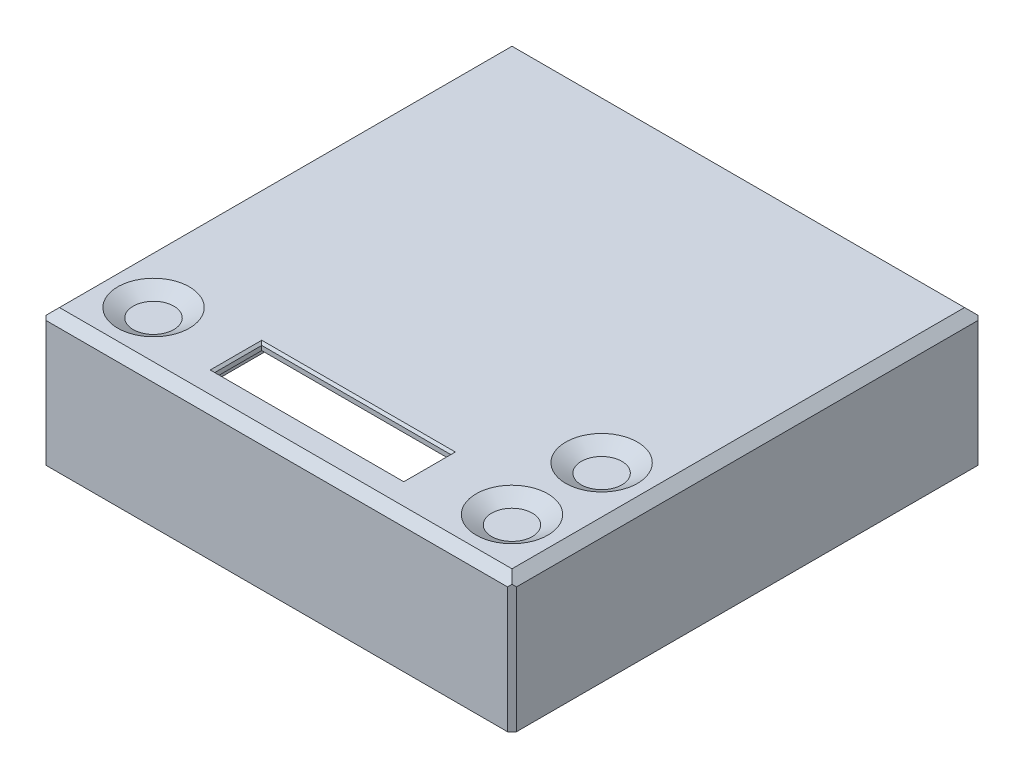
SolidWorks part; units mm, degrees
ref_plane "前视基准面" through (0, 0, 0) normal (0, 0, 1) x (1, 0, 0)
ref_plane "上视基准面" through (0, 0, 0) normal (0, 1, 0) x (1, 0, 0)
ref_plane "右视基准面" through (0, 0, 0) normal (1, 0, 0) x (0, 0, -1)
other "Configuration Table"
sketch "草图1" plane through (0, 0, 0) normal (0, 1, 0) x (1, 0, 0)
  line L0 (-45, 45) -> (45, 45) construction
  line L1 (-50, 50) -> (50, 50)
  line L2 (-50, 50) -> (-50, -50)
  line L3 (-50, -50) -> (50, -50)
  line L4 (50, 50) -> (50, -50)
  line L5 (-50, 50) -> (50, -50) construction
  line L6 (-50, -50) -> (50, 50) construction
  line L7 (-30, -30) -> (30, -30) construction
  line L8 (-40, -40) -> (40, -40) construction
  line L9 (40, -40) -> (40, -20) construction
  line L11 (28, -31) -> (-24, -31)
  line L12 (28, -31) -> (28, -49)
  line L13 (28, -49) -> (-24, -49)
  line L14 (-24, -31) -> (-24, -49)
  circle A0 centre (-45, 45) radius 1.75
  circle A1 centre (45, 45) radius 1.75
  circle A2 centre (-30, -30) radius 1.75
  circle A3 centre (30, -30) radius 1.75
  circle A4 centre (-40, -40) radius 5
  circle A5 centre (40, -40) radius 5
  circle A6 centre (40, -20) radius 5
  point P0 (0, 0)
  dimension "D4" = 3.5
  dimension "D8" = 10
  dimension "D1" = 100
  dimension "D2" = 100
  dimension "D3" = 5
  dimension "D5" = 20
  dimension "D6" = 10
  dimension "D7" = 20
  dimension "D9" = 52
  dimension "D10" = 18
  dimension "D11" = 1
  dimension "D12" = 22
sketch "草图2" plane through (0, 0, 0) normal (0, 1, 0) x (1, 0, 0)
  line L0 (50, 50) -> (50, -50) construction
  line L1 (-50.5, 50.5) -> (50.5, 50.5)
  line L2 (-50.5, 50.5) -> (-50.5, -50.5)
  line L3 (-50.5, -50.5) -> (50.5, -50.5)
  line L4 (50.5, 50.5) -> (50.5, -50.5)
  line L5 (-50.5, 50.5) -> (50.5, -50.5) construction
  line L6 (-50.5, -50.5) -> (50.5, 50.5) construction
  line L7 (-50, -50) -> (50, -50) construction
  line L9 (-52.5, 52.5) -> (52.5, 52.5)
  line L10 (-52.5, 52.5) -> (-52.5, -52.5)
  line L11 (-52.5, -52.5) -> (52.5, -52.5)
  line L12 (52.5, 52.5) -> (52.5, -52.5)
  line L13 (-52.5, 52.5) -> (52.5, -52.5) construction
  line L14 (-52.5, -52.5) -> (52.5, 52.5) construction
  point P0 (0, 0)
  point P10 (0, 0)
  dimension "D1" = 0.5
  dimension "D2" = 0.5
  dimension "D3" = 2
  dimension "D4" = 2
extrude "凸台-拉伸1" add sketch "草图2" against normal blind 25
extrude "凸台-拉伸2" add sketch "草图2<2>" along normal blind 5 contours L11 L12 L9 L10
sketch "草图2<2>" plane through (0, 0, 0) normal (0, 1, 0) x (1, 0, 0) same geometry as "草图2"
sketch "草图3" plane through (0, 0, 0) normal (0, 1, 0) x (1, 0, 0)
  line L0 (28, -31) -> (28, -49) construction
  line L1 (28, -49) -> (-24, -49) construction
  line L2 (-24, -31) -> (-24, -49) construction
  line L3 (28, -31) -> (-24, -31) construction
  line L4 (28, -31) -> (28, -35)
  line L5 (28, -49) -> (-24, -49)
  line L6 (-24, -31) -> (-24, -49)
  line L7 (28, -31) -> (-24, -31)
  line L8 (28, -35) -> (28, -45) construction
  line L9 (28, -35) -> (30, -35)
  line L10 (28, -35) -> (28, -45) construction
  line L11 (28, -45) -> (30, -45)
  line L12 (30, -35) -> (30, -45)
  line L13 (28, -45) -> (28, -49)
  circle A0 centre (-30, -30) radius 2
  circle A1 centre (-45, 45) radius 2
  circle A2 centre (45, 45) radius 2
  point P17 (-24, -40)
  point P18 (30, -40)
  dimension "D1" = 4
  dimension "D2" = 10
  dimension "D3" = 2
extrude "切除-拉伸1" cut sketch "草图3" along normal blind 3.5
sketch "草图4" plane through (0, 0, 0) normal (0, 1, 0) x (1, 0, 0)
  circle A0 centre (30, -30) radius 1.5
  dimension "D1" = 3
extrude "凸台-拉伸3" add sketch "草图4" against normal blind 3
sketch "草图6" plane through (0, 0, 0) normal (0, 0, 1) x (1, 0, 0)
  line L1 (4.5, -1.5) -> (-4.5, -1.5)
  line L2 (4.5, -1.5) -> (4.5, -4.7)
  line L3 (4.5, -4.7) -> (-4.5, -4.7)
  line L4 (-4.5, -1.5) -> (-4.5, -4.7)
  line L5 (4.5, -1.5) -> (-4.5, -4.7) construction
  line L6 (4.5, -4.7) -> (-4.5, -1.5) construction
  point P0 (0, -3.1)
  dimension "D1" = 1.5
  dimension "D2" = 9
  dimension "D3" = 3.2
extrude "切除-拉伸3" cut sketch "草图6" against normal through all
chamfer "倒角3" distance 2 angle 45 4 edges at (0, 5, 52.5) (52.5, 5, 0) (0, 5, -52.5) (-52.5, 5, 0)
chamfer "倒角2" distance 1 angle 45 4 edges at (-52.5, -11, -52.5) (52.5, -11, -52.5) (52.5, -11, 52.5) (-52.5, -11, 52.5)
sketch "草图7" plane through (0, 0, 0) normal (0, 1, 0) x (1, 0, 0)
  circle A0 centre (-40, -40) radius 8
  circle A1 centre (40, -40) radius 8
  circle A2 centre (40, -20) radius 8
  dimension "D1" = 16
extrude "切除-拉伸4" cut sketch "草图7" against normal blind 2 from surface starting at face at (0, 5, 0)
chamfer "倒角4" distance 2 angle 60 3 edges at (40, 3, 48) (40, 3, 28) (-40, 3, 48) first distance on face at (40, 3, 48) first distance on face at (40, 3, 28) first distance on face at (-40, 3, 48)
sketch "草图8" plane through (0, 0, 0) normal (0, 1, 0) x (1, 0, 0)
  line L0 (-40, -40) -> (40, -40) construction
  line L1 (-21.6, -34.25) -> (21.6, -34.25)
  line L2 (-21.6, -34.25) -> (-21.6, -45.75)
  line L3 (-21.6, -45.75) -> (21.6, -45.75)
  line L4 (21.6, -34.25) -> (21.6, -45.75)
  line L5 (-21.6, -34.25) -> (21.6, -45.75) construction
  line L6 (-21.6, -45.75) -> (21.6, -34.25) construction
  point P0 (0, -40)
  dimension "D1" = 43.2
  dimension "D2" = 11.5
extrude "切除-拉伸5" cut sketch "草图8" against normal blind 0.5 from surface starting at face at (-40, 5, 48)
chamfer "倒角5" distance 0.5 angle 45 4 edges at (0, 4.5, 45.75) (21.6, 4.5, 40) (-21.6, 4.5, 40) (0, 4.5, 34.25)
sketch "草图9" plane through (0, 0, 0) normal (0, 1, 0) x (1, 0, 0)
  line L0 (16.1333, -33.3167) -> (16.1333, -26.8167) construction
  line L1 (50.5, 35.4167) -> (35.4167, 35.4167)
  line L2 (50.5, 35.4167) -> (50.5, 39.5)
  line L3 (39.5, 50.5) -> (35.4167, 50.5)
  line L4 (35.4167, 35.4167) -> (35.4167, 50.5)
  line L5 (33.3167, 35.4167) -> (33.3167, 50.5)
  line L6 (33.3167, 35.4167) -> (18.2333, 35.4167)
  line L7 (18.2333, 35.4167) -> (18.2333, 50.5)
  line L8 (33.3167, 50.5) -> (18.2333, 50.5)
  line L9 (16.1333, 35.4167) -> (16.1333, 50.5)
  line L10 (16.1333, 35.4167) -> (1.05, 35.4167)
  line L11 (1.05, 35.4167) -> (1.05, 50.5)
  line L12 (16.1333, 50.5) -> (1.05, 50.5)
  line L13 (-1.05, 35.4167) -> (-1.05, 50.5)
  line L14 (-1.05, 35.4167) -> (-16.1333, 35.4167)
  line L15 (-16.1333, 35.4167) -> (-16.1333, 50.5)
  line L16 (-1.05, 50.5) -> (-16.1333, 50.5)
  line L17 (-18.2333, 35.4167) -> (-18.2333, 50.5)
  line L18 (-18.2333, 35.4167) -> (-33.3167, 35.4167)
  line L19 (-33.3167, 35.4167) -> (-33.3167, 50.5)
  line L20 (-18.2333, 50.5) -> (-33.3167, 50.5)
  line L21 (-35.4167, 35.4167) -> (-35.4167, 50.5)
  line L22 (-35.4167, 35.4167) -> (-50.5, 35.4167)
  line L23 (-50.5, 35.4167) -> (-50.5, 39.5)
  line L24 (-35.4167, 50.5) -> (-39.5, 50.5)
  line L25 (33.3167, 18.2333) -> (33.3167, 33.3167)
  line L26 (33.3167, 18.2333) -> (18.2333, 18.2333)
  line L27 (18.2333, 18.2333) -> (18.2333, 33.3167)
  line L28 (33.3167, 33.3167) -> (18.2333, 33.3167)
  line L29 (16.1333, 18.2333) -> (16.1333, 33.3167)
  line L30 (16.1333, 18.2333) -> (1.05, 18.2333)
  line L31 (1.05, 18.2333) -> (1.05, 33.3167)
  line L32 (16.1333, 33.3167) -> (1.05, 33.3167)
  line L33 (-1.05, 18.2333) -> (-1.05, 33.3167)
  line L34 (-1.05, 18.2333) -> (-16.1333, 18.2333)
  line L35 (-16.1333, 18.2333) -> (-16.1333, 33.3167)
  line L36 (-1.05, 33.3167) -> (-16.1333, 33.3167)
  line L37 (-18.2333, 18.2333) -> (-18.2333, 33.3167)
  line L38 (-18.2333, 18.2333) -> (-33.3167, 18.2333)
  line L39 (-33.3167, 18.2333) -> (-33.3167, 33.3167)
  line L40 (-18.2333, 33.3167) -> (-33.3167, 33.3167)
  line L41 (-35.4167, 18.2333) -> (-35.4167, 33.3167)
  line L42 (-35.4167, 18.2333) -> (-50.5, 18.2333)
  line L43 (-50.5, 18.2333) -> (-50.5, 33.3167)
  line L44 (-35.4167, 33.3167) -> (-50.5, 33.3167)
  line L45 (33.3167, 1.05) -> (33.3167, 16.1333)
  line L46 (33.3167, 1.05) -> (18.2333, 1.05)
  line L47 (18.2333, 1.05) -> (18.2333, 16.1333)
  line L48 (33.3167, 16.1333) -> (18.2333, 16.1333)
  line L49 (16.1333, 1.05) -> (16.1333, 16.1333)
  line L50 (16.1333, 1.05) -> (1.05, 1.05)
  line L51 (1.05, 1.05) -> (1.05, 16.1333)
  line L52 (16.1333, 16.1333) -> (1.05, 16.1333)
  line L53 (-1.05, 1.05) -> (-1.05, 16.1333)
  line L54 (-1.05, 1.05) -> (-16.1333, 1.05)
  line L55 (-16.1333, 1.05) -> (-16.1333, 16.1333)
  line L56 (-1.05, 16.1333) -> (-16.1333, 16.1333)
  line L57 (-18.2333, 1.05) -> (-18.2333, 16.1333)
  line L58 (-18.2333, 1.05) -> (-33.3167, 1.05)
  line L59 (-33.3167, 1.05) -> (-33.3167, 16.1333)
  line L60 (-18.2333, 16.1333) -> (-33.3167, 16.1333)
  line L61 (-35.4167, 1.05) -> (-35.4167, 16.1333)
  line L62 (-35.4167, 1.05) -> (-50.5, 1.05)
  line L63 (-50.5, 1.05) -> (-50.5, 16.1333)
  line L64 (-35.4167, 16.1333) -> (-50.5, 16.1333)
  line L65 (33.3167, -16.1333) -> (33.3167, -1.05)
  line L66 (33.3167, -16.1333) -> (18.2333, -16.1333)
  line L67 (18.2333, -16.1333) -> (18.2333, -1.05)
  line L68 (33.3167, -1.05) -> (18.2333, -1.05)
  line L69 (16.1333, -16.1333) -> (16.1333, -1.05)
  line L70 (16.1333, -16.1333) -> (1.05, -16.1333)
  line L71 (1.05, -16.1333) -> (1.05, -1.05)
  line L72 (16.1333, -1.05) -> (1.05, -1.05)
  line L73 (-1.05, -16.1333) -> (-1.05, -1.05)
  line L74 (-1.05, -16.1333) -> (-16.1333, -16.1333)
  line L75 (-16.1333, -16.1333) -> (-16.1333, -1.05)
  line L76 (-1.05, -1.05) -> (-16.1333, -1.05)
  line L77 (-18.2333, -16.1333) -> (-18.2333, -1.05)
  line L78 (-18.2333, -16.1333) -> (-33.3167, -16.1333)
  line L79 (-33.3167, -16.1333) -> (-33.3167, -1.05)
  line L80 (-18.2333, -1.05) -> (-33.3167, -1.05)
  line L81 (-35.4167, -16.1333) -> (-35.4167, -1.05)
  line L82 (-35.4167, -16.1333) -> (-50.5, -16.1333)
  line L83 (-50.5, -16.1333) -> (-50.5, -1.05)
  line L84 (-35.4167, -1.05) -> (-50.5, -1.05)
  line L85 (33.3167, -33.3167) -> (33.3167, -18.2333) construction
  line L86 (33.3167, -33.3167) -> (18.2333, -33.3167) construction
  line L87 (18.2333, -26.8167) -> (18.2333, -18.2333)
  line L88 (32, -18.2333) -> (18.2333, -18.2333)
  line L89 (16.1333, -26.8167) -> (16.1333, -18.2333)
  line L90 (16.1333, -33.3167) -> (1.05, -33.3167) construction
  line L91 (1.05, -26.8167) -> (1.05, -18.2333)
  line L92 (16.1333, -18.2333) -> (1.05, -18.2333)
  line L93 (-1.05, -26.8167) -> (-1.05, -18.2333)
  line L94 (-1.05, -33.3167) -> (-16.1333, -33.3167) construction
  line L95 (-16.1333, -26.8167) -> (-16.1333, -18.2333)
  line L96 (-1.05, -18.2333) -> (-16.1333, -18.2333)
  line L97 (-18.2333, -26.8167) -> (-18.2333, -18.2333)
  line L98 (-18.2333, -33.3167) -> (-33.3167, -33.3167) construction
  line L99 (-33.3167, -26.8167) -> (-33.3167, -18.2333)
  line L100 (-18.2333, -18.2333) -> (-33.3167, -18.2333)
  line L101 (-35.4167, -32) -> (-35.4167, -18.2333)
  line L102 (-35.4167, -33.3167) -> (-50.5, -33.3167) construction
  line L103 (-50.5, -32) -> (-50.5, -18.2333)
  line L104 (-35.4167, -18.2333) -> (-50.5, -18.2333)
  line L105 (33.3167, -50.5) -> (33.3167, -35.4167) construction
  line L106 (33.3167, -50.5) -> (18.2333, -50.5) construction
  line L107 (18.2333, -50.5) -> (18.2333, -35.4167) construction
  line L108 (33.3167, -35.4167) -> (18.2333, -35.4167) construction
  line L109 (16.1333, -50.5) -> (16.1333, -35.4167) construction
  line L110 (16.1333, -50.5) -> (1.05, -50.5) construction
  line L111 (1.05, -50.5) -> (1.05, -35.4167) construction
  line L112 (16.1333, -35.4167) -> (1.05, -35.4167) construction
  line L113 (-1.05, -50.5) -> (-1.05, -35.4167) construction
  line L114 (-1.05, -50.5) -> (-16.1333, -50.5) construction
  line L115 (-16.1333, -50.5) -> (-16.1333, -35.4167) construction
  line L116 (-1.05, -35.4167) -> (-16.1333, -35.4167) construction
  line L117 (-18.2333, -50.5) -> (-18.2333, -35.4167) construction
  line L118 (-18.2333, -50.5) -> (-33.3167, -50.5) construction
  line L119 (-33.3167, -50.5) -> (-33.3167, -35.4167) construction
  line L120 (-18.2333, -35.4167) -> (-33.3167, -35.4167) construction
  line L121 (-35.4167, -50.5) -> (-35.4167, -35.4167) construction
  line L122 (-35.4167, -50.5) -> (-50.5, -50.5) construction
  line L123 (-50.5, -50.5) -> (-50.5, -35.4167) construction
  line L124 (-35.4167, -35.4167) -> (-50.5, -35.4167) construction
  line L125 (50.5, 18.2333) -> (50.5, 33.3167)
  line L126 (50.5, 18.2333) -> (35.4167, 18.2333)
  line L127 (35.4167, 18.2333) -> (35.4167, 33.3167)
  line L128 (50.5, 33.3167) -> (35.4167, 33.3167)
  line L129 (50.5, 1.05) -> (50.5, 16.1333)
  line L130 (50.5, 1.05) -> (35.4167, 1.05)
  line L131 (35.4167, 1.05) -> (35.4167, 16.1333)
  line L132 (50.5, 16.1333) -> (35.4167, 16.1333)
  line L133 (50.5, -12) -> (50.5, -1.05)
  line L134 (50.5, -16.1333) -> (35.4167, -16.1333) construction
  line L135 (35.4167, -12) -> (35.4167, -1.05)
  line L136 (50.5, -1.05) -> (35.4167, -1.05)
  line L137 (50.5, -33.3167) -> (50.5, -18.2333) construction
  line L138 (50.5, -33.3167) -> (35.4167, -33.3167) construction
  line L139 (35.4167, -33.3167) -> (35.4167, -18.2333) construction
  line L140 (50.5, -18.2333) -> (35.4167, -18.2333) construction
  line L141 (50.5, -50.5) -> (50.5, -35.4167) construction
  line L142 (50.5, -50.5) -> (35.4167, -50.5) construction
  line L143 (35.4167, -50.5) -> (35.4167, -35.4167) construction
  line L144 (50.5, -35.4167) -> (35.4167, -35.4167) construction
  line L145 (-50.5, 50.5) -> (-50.5, -50.5) construction
  line L146 (-50.5, -50.5) -> (50.5, -50.5) construction
  line L147 (50.5, -50.5) -> (50.5, 50.5) construction
  line L148 (32, -26.8167) -> (18.2333, -26.8167)
  line L149 (32, -26.8167) -> (32, -18.2333)
  line L150 (50.5, -12) -> (35.4167, -12)
  line L151 (50.5, -16.1333) -> (50.5, -12) construction
  line L152 (35.4167, -16.1333) -> (35.4167, -12) construction
  line L153 (18.2333, -33.3167) -> (18.2333, -26.8167) construction
  line L154 (18.2333, -26.8167) -> (16.1333, -26.8167) construction
  line L155 (16.1333, -26.8167) -> (1.05, -26.8167)
  line L156 (1.05, -33.3167) -> (1.05, -26.8167) construction
  line L157 (1.05, -26.8167) -> (-1.05, -26.8167) construction
  line L158 (-1.05, -26.8167) -> (-16.1333, -26.8167)
  line L159 (-1.05, -33.3167) -> (-1.05, -26.8167) construction
  line L160 (-16.1333, -33.3167) -> (-16.1333, -26.8167) construction
  line L161 (-16.1333, -26.8167) -> (-18.2333, -26.8167) construction
  line L162 (-18.2333, -26.8167) -> (-33.3167, -26.8167)
  line L163 (-18.2333, -33.3167) -> (-18.2333, -26.8167) construction
  line L164 (-33.3167, -33.3167) -> (-33.3167, -26.8167) construction
  line L165 (-35.4167, -32) -> (-50.5, -32)
  line L166 (-35.4167, -33.3167) -> (-35.4167, -32) construction
  line L167 (-50.5, -33.3167) -> (-50.5, -32) construction
  line L168 (33.3167, -18.2333) -> (32, -18.2333) construction
  line L169 (50.5, 50.5) -> (45, 50.5) construction
  line L170 (50.5, 45) -> (50.5, 50.5) construction
  line L171 (-45, 50.5) -> (-50.5, 50.5) construction
  line L172 (-50.5, 45) -> (-50.5, 50.5) construction
  line L173 (-39.5, 45) -> (-39.5, 50.5)
  line L174 (-45, 39.5) -> (-50.5, 39.5)
  line L175 (39.5, 45) -> (39.5, 50.5)
  line L176 (45, 39.5) -> (50.5, 39.5)
  line L177 (-39.5, 50.5) -> (-45, 50.5) construction
  line L178 (-50.5, 39.5) -> (-50.5, 45) construction
  line L179 (45, 50.5) -> (39.5, 50.5) construction
  line L180 (50.5, 39.5) -> (50.5, 45) construction
  circle A0 centre (-40, -40) radius 8 construction
  arc A1 (39.5, 45) -> (45, 39.5) centre (45, 45) ccw
  circle A2 centre (40, -20) radius 8 construction
  arc A3 (-45, 39.5) -> (-39.5, 45) centre (-45, 45) ccw
  arc A4 (50.5, 45) -> (45, 50.5) centre (45, 45) ccw construction
  arc A5 (-45, 50.5) -> (-50.5, 45) centre (-45, 45) ccw construction
  arc A6 (-39.5, 45) -> (-45, 50.5) centre (-45, 45) ccw construction
  arc A7 (-50.5, 45) -> (-45, 39.5) centre (-45, 45) ccw construction
  arc A8 (45, 50.5) -> (39.5, 45) centre (45, 45) ccw construction
  arc A9 (45, 39.5) -> (50.5, 45) centre (45, 45) ccw construction
  dimension "D1" = 6
  dimension "D2" = 6
  dimension "D3" = 15.0833
  dimension "D4" = 15.0833
  dimension "D5" = 6.5
extrude "切除-拉伸6" cut sketch "草图9" along normal blind 3.5 from surface starting at face at (30, 0, 31.5)
sketch "草图10" plane through (0, 0, 0) normal (0, 1, 0) x (1, 0, 0)
  line L4 (-21.1, -34.75) -> (-21.1, -45.25)
  line L6 (-21.1, -34.75) -> (-21.1, -45.25)
  line L12 (-21.1, -45.25) -> (21.1, -45.25)
  line L14 (-21.1, -45.25) -> (21.1, -45.25)
  line L16 (21.1, -45.25) -> (21.1, -34.75)
  line L17 (21.1, -45.25) -> (21.1, -34.75)
  line L18 (21.1, -34.75) -> (-21.1, -34.75)
  line L19 (21.1, -34.75) -> (-21.1, -34.75)
  dimension "D1" = 0
extrude "切除-拉伸7" cut sketch "草图10" against normal up to next from surface starting at face at (0, 4.5, 40)
